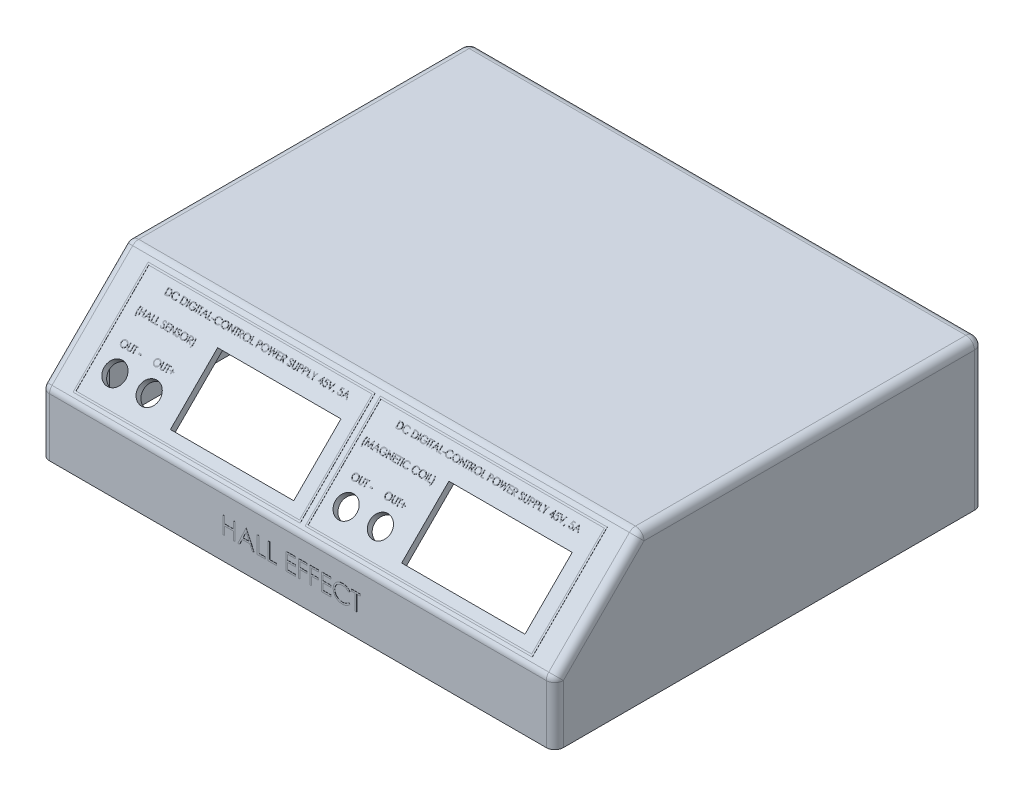
SolidWorks part; units mm, degrees
ref_plane "Front Plane" through (0, 0, 0) normal (0, 0, 1) x (1, 0, 0)
ref_plane "Top Plane" through (0, 0, 0) normal (0, 1, 0) x (1, 0, 0)
ref_plane "Right Plane" through (0, 0, 0) normal (1, 0, 0) x (0, 0, -1)
sketch "Sketch1" plane through (0, 0, 0) normal (0, 1, 0) x (1, 0, 0)
  line L1 (-150, 125) -> (150, 125)
  line L2 (-150, 125) -> (-150, -125)
  line L3 (-150, -125) -> (150, -125)
  line L4 (150, 125) -> (150, -125)
  line L5 (-150, 125) -> (150, -125) construction
  line L6 (-150, -125) -> (150, 125) construction
  point P0 (0, 0)
  dimension "D1" = 300
  dimension "D2" = 250
extrude "Boss-Extrude1" add sketch "Sketch1" along normal blind 86
chamfer "panel" distance 50 angle 45 1 edges at (0, 86, 125)
shell "Shell1" thickness 4 removed face at (0, 0, 0)
sketch "Sketch2" plane through (0, 0, 0) normal (0, -1, 0) x (1, 0, 0)
  line L1 (-146, -121) -> (-130, -121)
  line L2 (-146, -121) -> (-146, -105)
  line L3 (-146, -105) -> (-130, -105)
  line L4 (-130, -121) -> (-130, -105)
  line L5 (146, -121) -> (130, -121)
  line L6 (146, -121) -> (146, -105)
  line L7 (146, -105) -> (130, -105)
  line L8 (130, -121) -> (130, -105)
  dimension "D1" = 16
extrude "ax1" add sketch "Sketch2" against normal up to next
sketch "Sketch3" plane through (0, 0, 0) normal (0, -1, 0) x (1, 0, 0)
  line L1 (-146, 121) -> (-130, 121)
  line L2 (-146, 121) -> (-146, 105)
  line L3 (-146, 105) -> (-130, 105)
  line L4 (-130, 121) -> (-130, 105)
  line L5 (146, 121) -> (130, 121)
  line L6 (146, 121) -> (146, 105)
  line L7 (146, 105) -> (130, 105)
  line L8 (130, 121) -> (130, 105)
  dimension "D1" = 16
extrude "ax2" add sketch "Sketch3" against normal up to next
fillet "Fillet1" radius 5 11 edges at (0, 86, -125) (150, 86, -25) (0, 86, 75) (-150, 86, -25) (-150, 18, 125) (0, 36, 125) (150, 18, 125) (-150, 43, -125) (150, 43, -125) (-150, 61, 100) (150, 61, 100)
sketch "Sketch4" plane through (0, 0, -125) normal (0, 0, -1) x (-1, 0, 0)
  line L1 (88, 51) -> (115, 51)
  line L2 (88, 51) -> (88, 20)
  line L3 (88, 20) -> (115, 20)
  line L4 (115, 51) -> (115, 20)
  line L6 (150, 81) -> (150, 0) construction
  line L7 (-145, 0) -> (145, 0) construction
  dimension "D1" = 31
  dimension "D2" = 27
  dimension "D3" = 35
  dimension "D4" = 20
extrude "Power plug" cut sketch "Sketch4" against normal up to next
chamfer "Plug Chamfer1" distance 6 angle 45 2 edges at (-88, 20, -123) (-115, 20, -123)
sketch "Sketch5" plane through (0, 0, -125) normal (0, 0, -1) x (-1, 0, 0)
  line L0 (83.5, 35.4) -> (119.5, 35.4) construction
  line L1 (101.5, 35.4) -> (101.5, 20) construction
  line L2 (94, 20) -> (109, 20) construction
  circle A0 centre (83.5, 35.4) radius 2.9838
  circle A1 centre (119.5, 35.4) radius 2.9838
  dimension "D1" = 36
  dimension "D2" = 15.4
extrude "Plug screw" cut sketch "Sketch5" against normal up to next
sketch "Sketch6" plane through (0, 0, -125) normal (0, 0, -1) x (-1, 0, 0)
  line L0 (-93, 35.4) -> (83.5, 35.4) construction
  line L1 (-115, 51.4) -> (-93, 51.4)
  line L2 (-115, 51.4) -> (-115, 19.4)
  line L3 (-115, 19.4) -> (-93, 19.4)
  line L4 (-93, 51.4) -> (-93, 19.4)
  line L5 (-150, 0) -> (-150, 81) construction
  dimension "D3" = 35
  dimension "D1" = 22
  dimension "D2" = 32
extrude "Power switch" cut sketch "Sketch6" against normal up to next
sketch "Sketch12" plane through (0, 80.5, 80.5) normal (0, 0.7071, 0.7071) x (1, 0, 0)
  line L0 (-133, 2.0675) -> (-2.5, 2.0675)
  line L1 (-2.5, 2.0675) -> (-2.5, -57.9325)
  line L2 (-2.5, -57.9325) -> (-133, -57.9325)
  line L3 (-133, -57.9325) -> (-133, 2.0675)
  line L4 (-134, -58.9325) -> (-134, 3.0675)
  line L5 (-134, 3.0675) -> (-1.5, 3.0675)
  line L6 (-1.5, 3.0675) -> (-1.5, -58.9325)
  line L7 (-1.5, -58.9325) -> (-134, -58.9325)
  line L8 (-150, -60.8614) -> (-150, 5.7071) construction
  line L9 (2.5, 2.0675) -> (133, 2.0675)
  line L10 (133, 2.0675) -> (133, -57.9325)
  line L11 (133, -57.9325) -> (2.5, -57.9325)
  line L12 (2.5, -57.9325) -> (2.5, 2.0675)
  line L14 (150, 5.7071) -> (150, -60.8614) construction
  line L15 (1.5, 3.0675) -> (134, 3.0675)
  line L16 (134, 3.0675) -> (134, -58.9325)
  line L17 (134, -58.9325) -> (1.5, -58.9325)
  line L18 (1.5, -58.9325) -> (1.5, 3.0675)
  dimension "D3" = 60
  dimension "D5" = 17
  dimension "D7" = 5
  dimension "D4" = 17
  dimension "D6" = 1
extrude "rect" add sketch "Sketch12" along normal blind 0.1
sketch "Sketch7" plane through (0, 80.5, 80.5) normal (0, 0.7071, 0.7071) x (1, 0, 0)
  line L1 (125, -13.2218) -> (53, -13.2218)
  line L2 (125, -13.2218) -> (125, -52.2218)
  line L3 (125, -52.2218) -> (53, -52.2218)
  line L4 (53, -13.2218) -> (53, -52.2218)
  line L5 (89, -13.2218) -> (89, 7.7782) construction
  line L6 (-150, 7.7782) -> (150, 7.7782) construction
  line L7 (125, -32.7218) -> (150, -32.7218) construction
  line L8 (150, 7.7782) -> (150, -62.9325) construction
  dimension "D1" = 72
  dimension "D2" = 39
  dimension "D3" = 21
  dimension "D4" = 25
extrude "DSP3003-R" cut sketch "Sketch7" against normal up to next
sketch "Sketch16" plane through (0, 80.5, 80.5) normal (0, 0.7071, 0.7071) x (1, 0, 0)
  line L0 (14.5, -43.5948) -> (34.5, -43.5948) construction
  line L1 (2.5, 2.0675) -> (2.5, -57.9325) construction
  circle A0 centre (14.5, -43.5948) radius 6.25
  circle A1 centre (34.5, -43.5948) radius 6.25
  dimension "D1" = 12.5
  dimension "D2" = 20
  dimension "D3" = 12
extrude "Banana jack" cut sketch "Sketch16" against normal up to next
sketch "Sketch13" plane through (0, 80.5, 80.5) normal (0, 0.7071, 0.7071) x (1, 0, 0)
  text T0 "OUT+\r\n" font "Century Gothic" height 3.5
  text T1 "OUT <b>-</b>" font "Century Gothic" height 3.5
  text T2 "DC DIGITAL-CONTROL POWER SUPPLY 45V, 5A" font "Century Gothic" height 3.5
extrude "supply_label" add sketch "Sketch13" along normal blind 0.1
sketch "Sketch14" plane through (0, 0, 125) normal (0, 0, 1) x (1, 0, 0)
  text T0 "HALL EFFECT" font "Century Gothic" height 10
extrude "Title" add sketch "Sketch14" along normal blind 0.1
sketch "Sketch15" plane through (0, 0, -125) normal (0, 0, -1) x (-1, 0, 0)
  text T0 "POWER SWITCH" font "Century Gothic" height 5
  text T1 "220VAC, 5A, 50Hz" font "Century Gothic" height 5
extrude "Back side label" add sketch "Sketch15" along normal blind 0.1
pattern_linear "LPattern1" count 2 spacing 135 along (1, 0, 0) of "Banana jack", "DSP3003-R", "supply_label"
sketch "Sketch17" plane through (0, 80.5, 80.5) normal (0, 0.7071, 0.7071) x (1, 0, 0)
  text T0 "(HALL SENSOR)" font "Century Gothic" height 3.5
  text T1 "(MAGNETIC COIL)"
extrude "Label2" add sketch "Sketch17" along normal blind 0.1
equation "\"width\"= 300"
equation "\"D1@Sketch1\"=\"width\""
equation "\"depth\"= 250"
equation "\"D2@Sketch1\"=\"depth\""
equation "\"height\"= 100 - 14"
equation "\"D1@Boss-Extrude1\"=\"height\""
equation "\"panel_ang1\"=45"
equation "\"D2@panel\"=\"panel_ang1\""
equation "\"panel_depth1\"=50"
equation "\"D1@panel\"=\"panel_depth1\""
equation "\"r1\"=5"
equation "\"D1@Fillet1\"=\"r1\""
equation "\"ax_size\"=16"
equation "\"D1@Sketch3\"=\"ax_size\""
equation "\"D1@Sketch2\"=\"ax_size\""
equation "\"plug_cf1\"=6"
equation "\"D1@Plug Chamfer1\" = \"plug_cf1\""
equation "\"ac_plug_height\"=31"
equation "\"D1@Sketch4\"=\"ac_plug_height\""
equation "\"ac_plug_width\"=27"
equation "\"D2@Sketch4\"=\"ac_plug_width\""
equation "\"ac_plug_v_border\"= 35"
equation "\"D3@Sketch4\"=\"ac_plug_v_border\""
equation "\"ac_plug_h_border\"= 20"
equation "\"D4@Sketch4\"=\"ac_plug_h_border\""
equation "\"ac_plut_screw_dist\"=36"
equation "\"D1@Sketch5\"=\"ac_plut_screw_dist\""
equation "\"ac_plut_screw_h\"= 14.6 + 0.8"
equation "\"D2@Sketch5\"=\"ac_plut_screw_h\""
equation "\"ac_switch_width\"=22"
equation "\"D1@Sketch6\"=\"ac_switch_width\""
equation "\"ac_switch_height\"=32"
equation "\"D2@Sketch6\"=\"ac_switch_height\""
equation "\"D3@Sketch6\"=\"ac_plug_v_border\""
equation "\"rect1_w\"=65"
equation "\"rect1_h\"=60"
equation "\"D3@Sketch12\"=\"rect1_h\""
equation "\"rect1_left\"=20"
equation "\"rect2_right\"= 17"
equation "\"D5@Sketch12\"=\"rect2_right\""
equation "\"rect_between\"= 5"
equation "\"D7@Sketch12\"=\"rect_between\""
equation "\"D4@Sketch12\"=\"rect2_right\""
equation "\"banana_hole\"=12.5"
equation "\"D1@Sketch16\"=\"banana_hole\""
equation "\"banana_dist\"=20"
equation "\"D2@Sketch16\"=\"banana_dist\""
equation "\"banana_border\"= 12"
equation "\"D3@Sketch16\"=\"banana_border\""
equation "\"dsp_border\"= 25"
equation "\"D4@Sketch7\"=\"dsp_border\""
